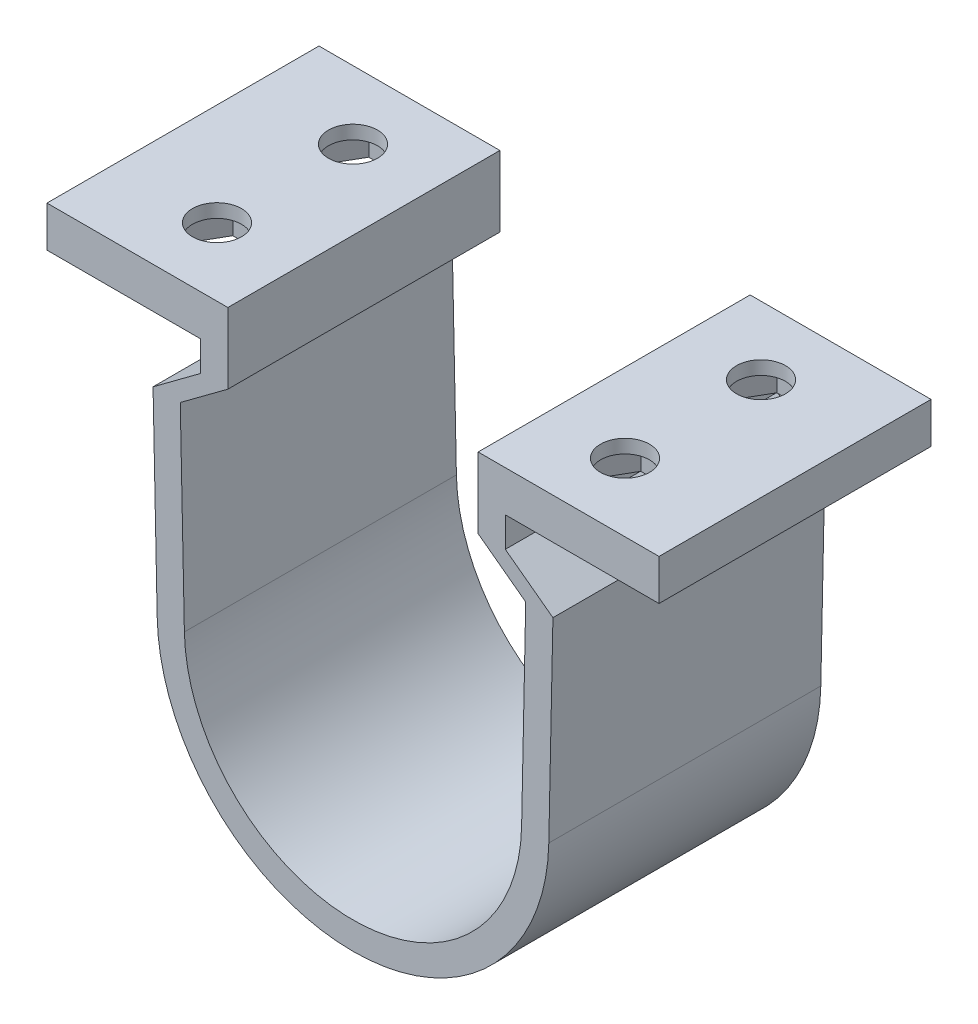
SolidWorks part; units mm, degrees
ref_plane "Front Plane" through (0, 0, 0) normal (0, 0, 1) x (1, 0, 0)
ref_plane "Top Plane" through (0, 0, 0) normal (0, 1, 0) x (1, 0, 0)
ref_plane "Right Plane" through (0, 0, 0) normal (1, 0, 0) x (0, 0, -1)
sketch "Sketch1" plane through (0, 0, 0) normal (0, 0, 1) x (1, 0, 0)
  line L0 (-22.5, 19) -> (-11.2, 19)
  line L1 (-14.7004, 14.2) -> (-14.3968, -0.3014)
  line L6 (-22.5, 19) -> (-22.5, 22)
  line L7 (-22.5, 22) -> (-9.2, 22)
  line L8 (-12.7, 14.2) -> (-12.3973, -0.2595)
  line L10 (-13.0466, 30.7547) -> (-12.3973, -0.2595) construction
  line L11 (12.4, 0) -> (12.4, 19) construction
  line L12 (0, 0) -> (0, 53.7575) construction
  line L13 (12.5, 14.2) -> (-12.5, 14.2) construction
  line L14 (-9, 14.2) -> (-9, 22.2) construction
  line L15 (-9, 22.2) -> (-22.5, 22.2) construction
  line L16 (-15, 27.2) -> (-15, 17.2) construction
  line L18 (-9.2, 16.7997) -> (-12.7, 14.2)
  line L21 (-15.0461, 30.7128) -> (-14.3968, -0.3014) construction
  line L23 (-12.25, 21) -> (-17.75, 21) construction
  line L25 (-9.2, 22) -> (-9.2, 16.7997)
  line L26 (-14.7004, 14.2) -> (-11.2, 16.8)
  line L27 (-11.2, 16.8) -> (-11.2, 19)
  line L29 (14.4, 0) -> (14.4, 19) construction
  line L30 (12.7, 14.2) -> (12.3973, -0.2595)
  line L31 (9.2, 16.7997) -> (12.7, 14.2)
  line L32 (9.2, 22) -> (9.2, 16.7997)
  line L33 (22.5, 22) -> (9.2, 22)
  line L34 (22.5, 19) -> (22.5, 22)
  line L35 (22.5, 19) -> (11.2, 19)
  line L36 (11.2, 16.8) -> (11.2, 19)
  line L37 (14.7004, 14.2) -> (11.2, 16.8)
  line L38 (14.7004, 14.2) -> (14.3968, -0.3014)
  arc A0 (-14.3968, -0.3014) -> (14.3968, -0.3014) centre (0, 0) ccw
  arc A1 (-12.3973, -0.2595) -> (12.3973, -0.2595) centre (0, 0) ccw
  circle A2 centre (0, 0) radius 12.2 construction
  arc A4 (-14.3968, -0.3014) -> (14.4, 0) centre (0, 0) ccw construction
  arc A5 (-12.3973, -0.2595) -> (12.4, 0) centre (0, 0) ccw construction
  point P17 (0, 12.2)
  point P22 (0, 14.2)
  point P29 (-15, 22.2)
  point P30 (-12.7, 14.2)
  point P41 (-15, 21)
  dimension "D3" = 24.4
  dimension "D4" = 0.2
  dimension "D2" = 3
  dimension "D5" = 25
  dimension "D6" = 2
  dimension "D7" = 3.5
  dimension "D8" = 8
  dimension "D9" = 13.5
  dimension "D10" = 7.5
  dimension "D11" = 0.2
  dimension "D12" = 0.2
  dimension "D13" = 0.2
  dimension "D14" = 10
  dimension "D15" = 5.5
  dimension "D16" = 2
  dimension "D17" = 1
  dimension "D18" = 2.2
  dimension "D1" = 2
extrude "Boss-Extrude1" add sketch "Sketch1" along normal blind 20
sketch "Sketch4" plane through (0, 19, 0) normal (0, -1, 0) x (1, 0, 0)
  line L0 (0, 0) -> (0, 20) construction
  line L1 (-13.4123, 2.25) -> (-11.8246, 5)
  line L2 (-11.8246, 5) -> (-13.4123, 7.75)
  line L3 (-13.4123, 7.75) -> (-16.5877, 7.75)
  line L4 (-16.5877, 7.75) -> (-18.1754, 5)
  line L5 (-18.1754, 5) -> (-16.5877, 2.25)
  line L6 (-16.5877, 2.25) -> (-13.4123, 2.25)
  line L7 (-11.8246, 15) -> (-13.4123, 17.75)
  line L8 (-13.4123, 17.75) -> (-16.5877, 17.75)
  line L9 (-16.5877, 17.75) -> (-18.1754, 15)
  line L10 (-18.1754, 15) -> (-16.5877, 12.25)
  line L11 (-16.5877, 12.25) -> (-13.4123, 12.25)
  line L12 (-13.4123, 12.25) -> (-11.8246, 15)
  line L13 (-14.3968, 0) -> (14.3968, 0) construction
  line L14 (14.3968, 20) -> (-14.3968, 20) construction
  line L15 (-22.5, 0) -> (-11.2, 0) construction
  line L16 (-22.5, 20) -> (-22.5, 0) construction
  line L17 (13.4123, 12.25) -> (11.8246, 15)
  line L18 (16.5877, 12.25) -> (13.4123, 12.25)
  line L19 (18.1754, 15) -> (16.5877, 12.25)
  line L20 (16.5877, 17.75) -> (18.1754, 15)
  line L21 (13.4123, 17.75) -> (16.5877, 17.75)
  line L22 (11.8246, 15) -> (13.4123, 17.75)
  line L23 (16.5877, 2.25) -> (13.4123, 2.25)
  line L24 (18.1754, 5) -> (16.5877, 2.25)
  line L25 (16.5877, 7.75) -> (18.1754, 5)
  line L26 (13.4123, 7.75) -> (16.5877, 7.75)
  line L27 (11.8246, 5) -> (13.4123, 7.75)
  line L28 (13.4123, 2.25) -> (11.8246, 5)
  circle A0 centre (-15, 5) radius 2.75 construction
  circle A1 centre (-15, 15) radius 2.75 construction
  dimension "D1" = 5.5
  dimension "D2" = 10
  dimension "D3" = 7.5
  dimension "D4" = 5
extrude "Cut-Extrude1" cut sketch "Sketch4" against normal blind 2
sketch "Sketch5" plane through (0, 19, 0) normal (0, -1, 0) x (-1, 0, 0)
  line L0 (0, -20) -> (0, 0) construction
  line L1 (-14.3968, -20) -> (14.3968, -20) construction
  line L3 (-22.5, -10) -> (22.5, -10) construction
  line L4 (-22.5, -20) -> (-22.5, 0) construction
  line L5 (22.5, -20) -> (22.5, 0) construction
  line L7 (-15, -15) -> (-17.3816, -13.625) construction
  line L8 (-16.5877, -12.25) -> (-18.1754, -15) construction
  line L10 (-15, -15) -> (-15, -12.25) construction
  line L11 (-13.4123, -12.25) -> (-16.5877, -12.25) construction
  point P0 (-15, -15)
  point P41 (15, -15)
  point P43 (-15, -5)
  point P44 (15, -5)
hole_wizard "M3 Clearance Hole1" positions "Sketch5" profile "Sketch6" hole size "M3" standard "ANSI Metric" end condition through all
sketch "Sketch6" plane through (15, 19, 15) normal (1, 0, 0) x (0, 0, -1)
  line L0 (0, 0) -> (0, 3)
  line L1 (0, 3) -> (1.8, 3)
  line L2 (1.8, 3) -> (1.8, 0)
  line L5 (1.8, 0) -> (0, 0)
  line L11 (0, -6.35) -> (0, 107.95) construction
  dimension "Thru Hole Dia." = 3.6
  dimension "Thru Hole Depth" = 3
